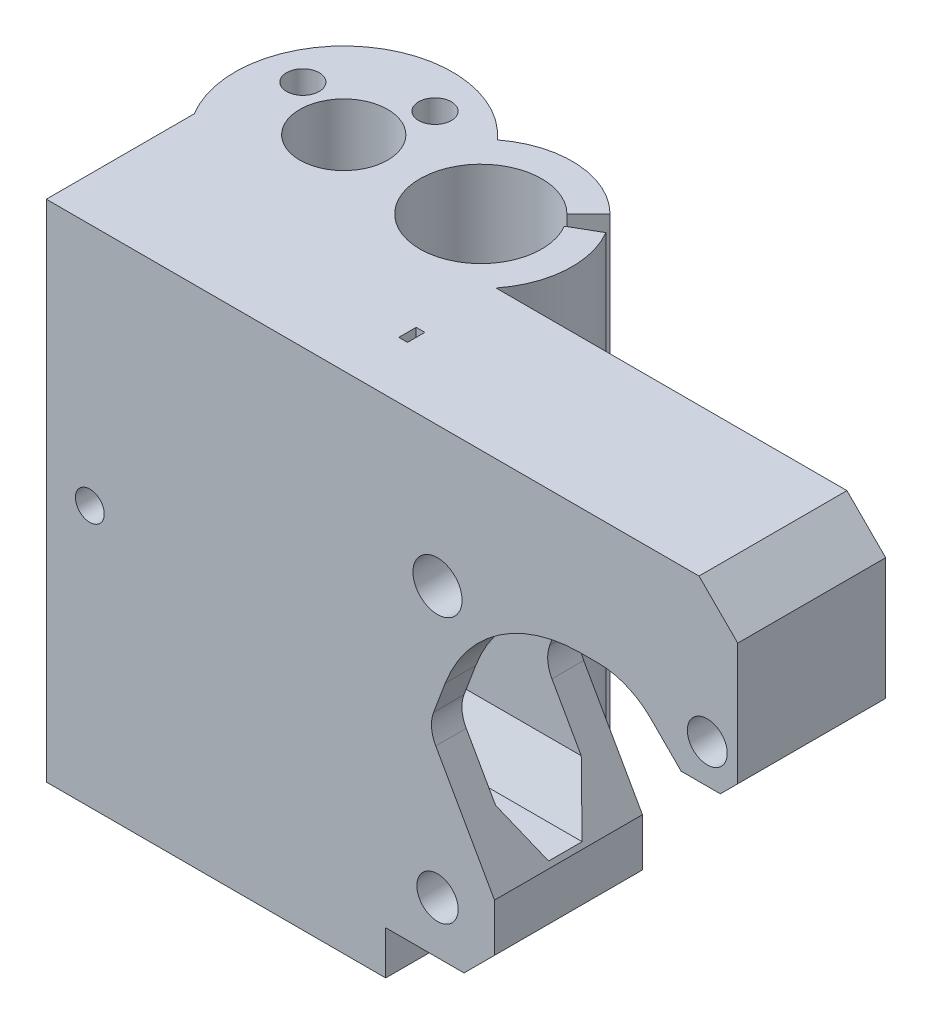
SolidWorks part; units mm, degrees
ref_plane "Front Plane" through (0, 0, 0) normal (0, 0, 1) x (1, 0, 0)
ref_plane "Top Plane" through (0, 0, 0) normal (0, 1, 0) x (1, 0, 0)
ref_plane "Right Plane" through (0, 0, 0) normal (1, 0, 0) x (0, 0, -1)
sketch "Sketch1" plane through (0, 0, 0) normal (0, 0, 1) x (1, 0, 0)
  line L0 (39, -53) -> (48, -53)
  line L1 (0, 0) -> (39, 0)
  line L2 (0, 0) -> (0, -58)
  line L3 (0, -58) -> (39, -58)
  line L4 (39, -53) -> (39, -58)
  line L5 (39, 0) -> (75, 0)
  line L6 (75, 0) -> (79.45, -4.45)
  line L7 (79.45, -4.45) -> (79.45, -18.45)
  line L8 (79.45, -18.45) -> (77.45, -20.45)
  line L9 (77.45, -20.45) -> (72.95, -20.45)
  line L10 (72.95, -20.45) -> (69.45, -16.95)
  line L12 (45.8405, -25.2376) -> (44.5009, -28.8048)
  line L13 (44.75, -32.0294) -> (51.5, -44)
  line L14 (51.5, -44) -> (51.5, -49.5)
  line L15 (61.4145, -14.45) -> (63.4145, -14.45)
  line L16 (51.5, -49.5) -> (48, -53)
  arc A5 (63.4145, -14.45) -> (69.45, -16.95) centre (63.4145, -22.9855) cw
  arc A6 (61.4145, -14.45) -> (45.8405, -25.2376) centre (61.4145, -31.0859) ccw
  arc A7 (44.5009, -28.8048) -> (44.75, -32.0294) centre (48.083, -30.15) ccw
  dimension "D1" = 58
  dimension "D2" = 39
  dimension "D3" = 75
  dimension "D4" = 4.45
  dimension "D5" = 135
  dimension "D6" = 14
  dimension "D7" = 2
  dimension "D8" = 3.5
  dimension "D9" = 6
  dimension "D10" = 5
  dimension "D11" = 4.5
  dimension "D12" = 130
  dimension "D13" = 3.5
  dimension "D14" = 5.5
  dimension "D15" = 6.75
  dimension "D16" = 9
  dimension "D17" = 13.85
  dimension "D18" = 3.417
  dimension "D19" = 2
extrude "Boss-Extrude1" add sketch "Sketch1" along normal blind 17
sketch "Sketch2" plane through (0, 0, 0) normal (0, 1, 0) x (1, 0, 0)
  line L0 (0, -17) -> (0, 6.5) construction
  line L1 (0, 6.5) -> (26.427, 6.5) construction
  circle A0 centre (26.427, 6.5) radius 10.5
  dimension "D2" = 21
  dimension "D1" = 23.5
  dimension "D3" = 26.427
extrude "Boss-Extrude2" add sketch "Sketch2" against normal up to surface (58 mm away) up to face at (19.5, -58, 8.5)
sketch "Sketch3" plane through (0, 0, 0) normal (0, 1, 0) x (1, 0, 0)
  line L0 (0, -17) -> (0, 20.4292) construction
  line L1 (10.6771, 6.5) -> (0, 6.5) construction
  line L2 (75, -17) -> (0, -17) construction
  circle A0 centre (10.6771, 6.5) radius 12.5
  dimension "D3" = 25
  dimension "D2" = 23.5
extrude "Boss-Extrude3" add sketch "Sketch3" against normal blind 13.5
sketch "Sketch4" plane through (0, 0, 0) normal (0, 1, 0) x (1, 0, 0)
  circle A0 centre (26.427, 6.5) radius 7
  circle A1 centre (10.6771, 6.5) radius 5.05
  dimension "D1" = 10.1
  dimension "D2" = 14
extrude "Cut-Extrude1" cut sketch "Sketch4" against normal through all
sketch "Sketch5" plane through (0, 0, 0) normal (-1, 0, 0) x (0, 0, 1)
  line L0 (10.5, -43.5) -> (6.65, -43.5)
  line L1 (6.65, -43.5) -> (3.65, -38)
  line L2 (3.65, -38) -> (3.65, -19)
  line L3 (3.65, -19) -> (6.65, -16)
  line L4 (6.65, -16) -> (10.5, -16)
  line L5 (10.5, -16) -> (13.5, -19)
  line L6 (13.5, -19) -> (13.5, -38)
  line L7 (13.5, -38) -> (10.5, -43.5)
  line L8 (17, 0) -> (0, 0) construction
  line L9 (17, 0) -> (17, -58) construction
  circle A0 centre (8.5, -6) radius 4.05
  circle A1 centre (8.5, -51) radius 4.05
  dimension "D8" = 8.1
  dimension "D9" = 8.1
  dimension "D1" = 19
  dimension "D2" = 3
  dimension "D3" = 3.85
  dimension "D4" = 16
  dimension "D5" = 6
  dimension "D6" = 51
  dimension "D7" = 5.5
  dimension "D10" = 3
  dimension "D11" = 3
  dimension "D12" = 19
  dimension "D13" = 3.85
  dimension "D14" = 3
  dimension "D15" = 3
  dimension "D16" = 3.5
  dimension "D17" = 8.5
  dimension "D18" = 8.5
extrude "Cut-Extrude2" cut sketch "Sketch5" against normal blind 35
sketch "Sketch6" plane through (0, 0, 0) normal (0, 0, -1) x (-1, 0, 0)
  line L0 (-75.9503, -16.0252) -> (-44.9503, -16.0252) construction
  line L1 (-44.9503, -16.0252) -> (-44.9503, -47.0252) construction
  line L2 (-44.9503, -47.0252) -> (-75.9503, -47.0252) construction
  line L3 (-75.9503, -47.0252) -> (-75.9503, -16.0252) construction
  line L4 (-75.9503, -31.5252) -> (-44.9503, -31.5252) construction
  line L5 (-60.4503, -16.0252) -> (-60.4503, -47.0252) construction
  circle A0 centre (-75.9503, -16.0252) radius 2.2933
  circle A1 centre (-44.9503, -16.0252) radius 2.8225
  circle A2 centre (-44.9503, -47.0252) radius 2.3733
  circle A3 centre (-60.4503, -31.5252) radius 11 construction
  point P14 (-60.4503, -31.5252)
  dimension "D3" = 22
  dimension "D1" = 31
  dimension "D2" = 31
extrude "Cut-Extrude3" cut sketch "Sketch6" against normal through all
sketch "Sketch8" plane through (35, 0, 0) normal (-1, 0, 0) x (0, 0, 1)
  line L8 (10.5, -43.5) -> (13.5, -38)
  line L9 (13.5, -38) -> (13.5, -19)
  line L10 (13.5, -19) -> (10.5, -16)
  line L11 (10.5, -16) -> (6.65, -16)
  line L12 (6.65, -16) -> (3.65, -19)
  line L13 (3.65, -19) -> (3.65, -38)
  line L14 (3.65, -38) -> (6.65, -43.5)
  line L15 (6.65, -43.5) -> (10.5, -43.5)
  line L16 (10.5, -43.5) -> (13.5, -38)
  line L17 (13.5, -38) -> (13.5, -19)
  line L18 (13.5, -19) -> (10.5, -16)
  line L19 (10.5, -16) -> (6.65, -16)
  line L20 (6.65, -16) -> (3.65, -19)
  line L21 (3.65, -19) -> (3.65, -38)
  line L22 (3.65, -38) -> (6.65, -43.5)
  line L23 (6.65, -43.5) -> (10.5, -43.5)
  dimension "D1" = 0
extrude "Cut-Extrude4" cut sketch "Sketch8" against normal blind 20
sketch "Sketch9" plane through (0, 0, 0) normal (0, 1, 0) x (1, 0, 0)
  line L0 (32.4461, 10.0735) -> (35.4774, 11.8236)
  line L1 (31.3767, 11.4497) -> (33.8516, 13.9246)
  line L2 (26.427, 6.5) -> (36.927, 6.5) construction
  line L3 (32.4461, 10.0735) -> (26.427, 6.5) construction
  line L4 (26.427, 6.5) -> (31.3767, 11.4497) construction
  arc A0 (32.4461, 10.0735) -> (31.3767, 11.4497) centre (26.427, 6.5) ccw
  arc A1 (35.4774, 11.8236) -> (33.8516, 13.9246) centre (26.427, 6.5) ccw
  arc A2 (34.6732, 0) -> (20.0124, 14.8128) centre (26.427, 6.5) ccw construction
  circle A3 centre (26.427, 6.5) radius 7 construction
  dimension "D1" = 15
  dimension "D2" = 30
extrude "Cut-Extrude5" cut sketch "Sketch9" against normal through all
sketch "Sketch10" plane through (0, 0, 0) normal (0, 1, 0) x (1, 0, 0)
  line L0 (13.5702, 14.0925) -> (10.6771, 6.5) construction
  line L1 (10.6771, 6.5) -> (3.0846, 9.3931) construction
  circle A0 centre (13.5702, 14.0925) radius 1.875
  circle A1 centre (3.0846, 9.3931) radius 1.875
  dimension "D3" = 3.75
  dimension "D4" = 3.75
  dimension "D1" = 90
  dimension "D2" = 8.125
  dimension "D5" = 8.125
extrude "Cut-Extrude6" cut sketch "Sketch10" against normal through all
sketch "Sketch11" plane through (0, -58, 0) normal (0, -1, 0) x (1, 0, 0)
  line L0 (0, 17) -> (0, 0) construction
  line L1 (35, 8.5) -> (34, 8.5)
  line L2 (35, 8.5) -> (35, 10.5)
  line L3 (35, 10.5) -> (34, 10.5)
  line L4 (34, 8.5) -> (34, 10.5)
  line L5 (0, 17) -> (39, 17) construction
  dimension "D1" = 35
  dimension "D2" = 1
  dimension "D3" = 2
  dimension "D4" = 6.5
extrude "Cut-Extrude7" cut sketch "Sketch11" against normal blind 8
ref_plane "Plane1" through (0, -29, 0) normal (0, 1, 0) x (1, 0, 0)
mirror "Mirror1" about plane through (0, -29, 0) normal (0, 1, 0) of "Cut-Extrude7"
sketch "Sketch12" plane through (0, 0, 17) normal (0, 0, 1) x (1, 0, 0)
  line L0 (0, 0) -> (0, -58) construction
  line L2 (75, 0) -> (0, 0) construction
  circle A0 centre (5, -28) radius 1.6588
  dimension "D1" = 3.3175
  dimension "D2" = 5
  dimension "D3" = 28
extrude "Cut-Extrude8" cut sketch "Sketch12" against normal through all
